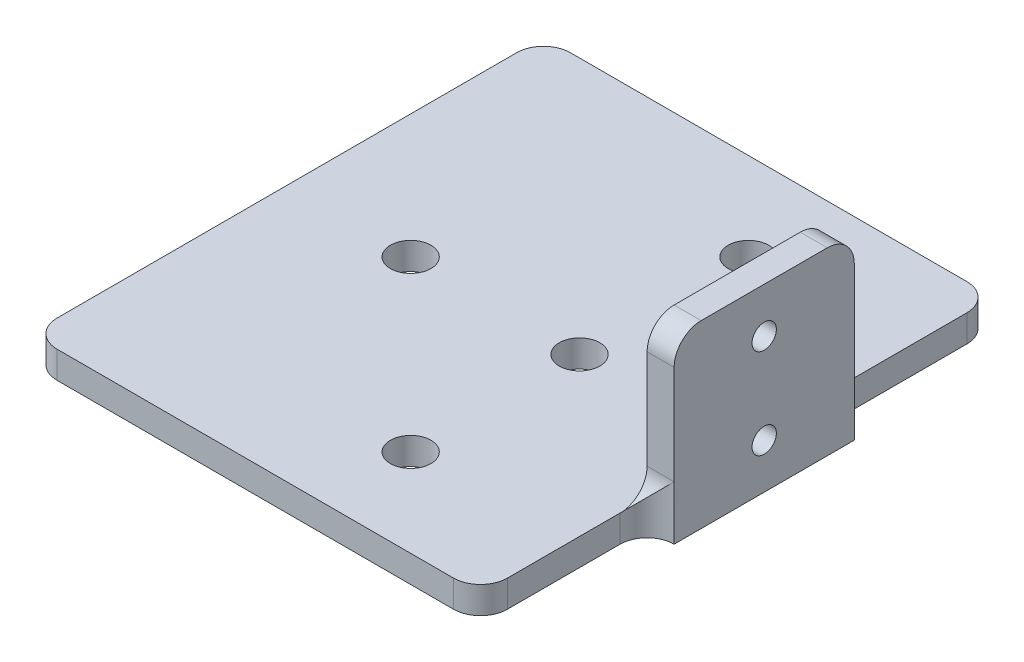
SolidWorks part; units mm, degrees
ref_plane "Front Plane" through (0, 0, 0) normal (0, 0, 1) x (1, 0, 0)
ref_plane "Top Plane" through (0, 0, 0) normal (0, 1, 0) x (1, 0, 0)
ref_plane "Right Plane" through (0, 0, 0) normal (1, 0, 0) x (0, 0, -1)
sketch "Sketch1" plane through (0, 0, 0) normal (0, 1, 0) x (1, 0, 0)
  line L1 (-25, 28.5) -> (25, 28.5)
  line L2 (-25, 28.5) -> (-25, -28.5)
  line L3 (-25, -28.5) -> (25, -28.5)
  line L4 (25, 28.5) -> (25, -28.5)
  line L5 (-25, 28.5) -> (25, -28.5) construction
  line L6 (-25, -28.5) -> (25, 28.5) construction
  point P0 (0, 0)
  point P6 (-11.25, 0)
  point P7 (7.5, 0)
  point P8 (26.25, 18.75)
  point P9 (26.25, -18.75)
  dimension "D1" = 50
  dimension "D2" = 57
  dimension "D3" = 13.75
  dimension "D4" = 18.75
  dimension "D5" = 18.75
  dimension "D6" = 18.75
  dimension "D7" = 18.75
extrude "Boss-Extrude1" add sketch "Sketch1" along normal blind 3
sketch "Sketch2" plane through (0, 3, 0) normal (0, 1, 0) x (1, 0, 0)
  point P0 (-11.25, 0)
  point P1 (7.5, 0)
  point P3 (26.25, 18.75)
  point P5 (26.25, -18.75)
  point P9 (26.25, 0)
  point P11 (7.5, 18.75)
  point P13 (-11.25, 18.75)
  point P15 (-11.25, -18.75)
  point P17 (7.5, -18.75)
hole_wizard "Ø4.5 (4.5) Diameter Hole1" positions "Sketch2" profile "Sketch3" hole size "Ø4.5" standard "ANSI Metric"
sketch "Sketch3" plane through (-11.25, 3, 0) normal (1, 0, 0) x (0, 0, 1)
  line L0 (0, 0) -> (0, 16.3519)
  line L1 (0, 16.3519) -> (2.25, 15)
  line L2 (2.25, 15) -> (2.25, 0)
  line L5 (2.25, 0) -> (0, 0)
  line L10 (0, 16.3519) -> (-2.25, 15) construction
  line L11 (0, -6.35) -> (0, 107.95) construction
  dimension "Hole Dia." = 4.5
  dimension "Hole Depth" = 15
  dimension "Drill Angle" = 118
sketch "Sketch4" plane through (25, 0, 0) normal (1, 0, 0) x (0, 0, -1)
  line L0 (-28.5, 0) -> (28.5, 0) construction
  line L1 (-10, 20) -> (10, 20)
  line L2 (-10, 20) -> (-10, 0)
  line L3 (-10, 0) -> (10, 0)
  line L4 (10, 20) -> (10, 0)
  line L5 (-10, 20) -> (10, 0) construction
  line L6 (-10, 0) -> (10, 20) construction
  point P0 (0, 10)
  dimension "D1" = 20
  dimension "D2" = 20
extrude "Boss-Extrude2" add sketch "Sketch4" along normal blind 3
sketch "Sketch5" plane through (28, 0, 0) normal (1, 0, 0) x (0, 0, -1)
  line L0 (-10, 10) -> (10, 10) construction
  line L1 (-10, 20) -> (-10, 0) construction
  line L2 (10, 0) -> (10, 20) construction
  line L3 (0, 15) -> (0, 5) construction
  point P10 (0, 10)
  point P11 (0, 15)
  point P12 (0, 5)
  dimension "D1" = 10
hole_wizard "Ø2.7 (2.7) Diameter Hole1" positions "Sketch5" profile "Sketch6" hole size "Ø2.7" standard "ANSI Metric"
sketch "Sketch6" plane through (28, 5, 0) normal (0, 1, 0) x (0, 0, -1)
  line L0 (0, 0) -> (0, 15.8112)
  line L1 (0, 15.8112) -> (1.35, 15)
  line L2 (1.35, 15) -> (1.35, 0)
  line L5 (1.35, 0) -> (0, 0)
  line L10 (0, 15.8112) -> (-1.35, 15) construction
  line L11 (0, -6.35) -> (0, 107.95) construction
  dimension "Hole Dia." = 2.7
  dimension "Hole Depth" = 15
  dimension "Drill Angle" = 118
fillet "Fillet1" radius 3 8 edges at (-25, 1.5, 28.5) (-25, 1.5, -28.5) (25, 1.5, -28.5) (25, 1.5, -10) (25, 1.5, 28.5) (25, 1.5, 10) (26.5, 20, -10) (26.5, 20, 10)
fillet "Fillet2" radius 3 2 edges at (26.5, 3, 10) (26.5, 3, -10)
